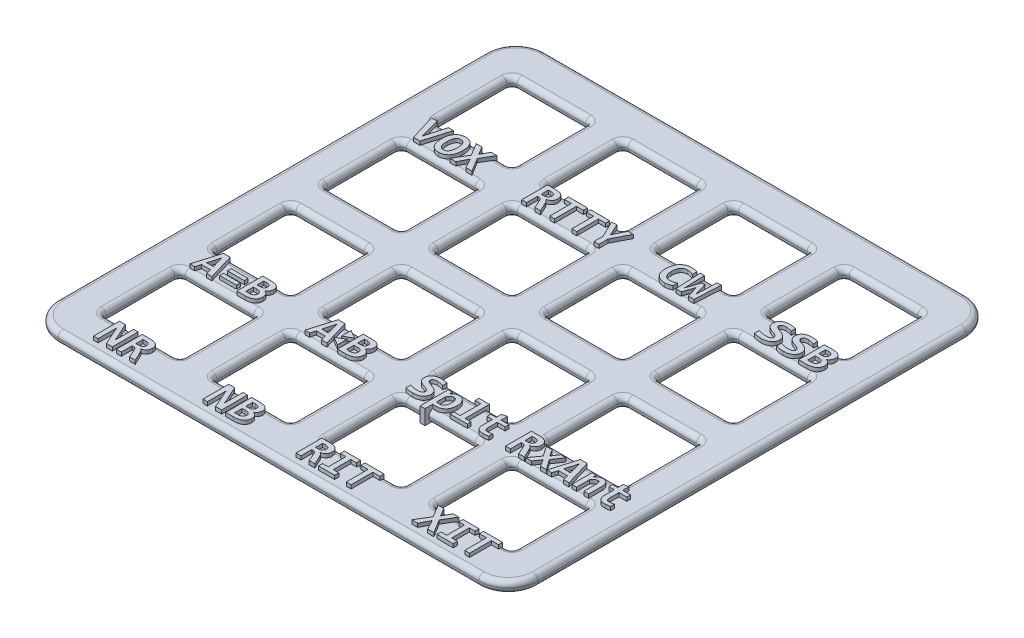
SolidWorks part; units mm, degrees
ref_plane "Front" through (0, 0, 0) normal (0, 0, 1) x (1, 0, 0)
ref_plane "Top" through (0, 0, 0) normal (0, 1, 0) x (1, 0, 0)
ref_plane "Right" through (0, 0, 0) normal (1, 0, 0) x (0, 0, -1)
sketch "Sketch1" plane through (0, 0, 0) normal (0, 1, 0) x (1, 0, 0)
  line L1 (-14.8807, -14.5355) -> (42.1193, -14.5355)
  line L2 (-18.8807, -18.5355) -> (-18.8807, -76.5355)
  line L3 (-14.8807, -80.5355) -> (42.1193, -80.5355)
  line L4 (46.1193, -18.5355) -> (46.1193, -76.5355)
  arc A0 (-14.8807, -14.5355) -> (-18.8807, -18.5355) centre (-14.8807, -18.5355) ccw
  arc A1 (46.1193, -18.5355) -> (42.1193, -14.5355) centre (42.1193, -18.5355) ccw
  arc A2 (42.1193, -80.5355) -> (46.1193, -76.5355) centre (42.1193, -76.5355) ccw
  arc A3 (-18.8807, -76.5355) -> (-14.8807, -80.5355) centre (-14.8807, -76.5355) ccw
  dimension "D1" = 65
  dimension "D2" = 66
extrude "main" add sketch "Sketch1" along normal blind 1.5
sketch "Sketch2" plane through (0, 1.5, 0) normal (0, 1, 0) x (1, 0, 0)
  line L0 (42.1193, -14.5355) -> (-14.8807, -14.5355) construction
  line L1 (-14.2307, -19.6855) -> (-3.5307, -19.6855)
  line L2 (-14.2307, -19.6855) -> (-14.2307, -30.3855)
  line L3 (-14.2307, -30.3855) -> (-3.5307, -30.3855)
  line L4 (-3.5307, -19.6855) -> (-3.5307, -30.3855)
  line L5 (-18.8807, -18.5355) -> (-18.8807, -76.5355) construction
  point P4 (-8.8807, -19.6855)
  dimension "D1" = 5.15
  dimension "D2" = 4.65
  dimension "D3" = 10.7
  dimension "D4" = 10.7
extrude "button hole 1" cut sketch "Sketch2" against normal through all
fillet "button fillet" radius 0.7 12 edges at (-8.8807, 0, 30.3855) (-8.8807, 1.5, 30.3855) (-8.8807, 0, 19.6855) (-8.8807, 1.5, 19.6855) (-3.5307, 0.75, 30.3855) (-3.5307, 0, 25.0355) (-3.5307, 0.75, 19.6855) (-3.5307, 1.5, 25.0355) (-14.2307, 0.75, 19.6855) (-14.2307, 0, 25.0355) (-14.2307, 0.75, 30.3855) (-14.2307, 1.5, 25.0355)
pattern_linear "buttons by 16" count 4 spacing 15 along (1, 0, 0) count 4 spacing 15 along (0, 0, 1) of "button fillet", "button hole 1"
fillet "outer edge fillet" radius 0.7 16 edges at (13.6193, 1.5, 14.5355) (13.6193, 0, 14.5355) (46.1193, 1.5, 47.5355) (46.1193, 0, 47.5355) (13.6193, 1.5, 80.5355) (13.6193, 0, 80.5355) (-18.8807, 1.5, 47.5355) (-18.8807, 0, 47.5355) (44.9477, 1.5, 15.7071) (44.9477, 1.5, 79.364) (-17.7092, 1.5, 79.364) (-17.7092, 1.5, 15.7071) (44.9477, 0, 15.7071) (44.9477, 0, 79.364) (-17.7092, 0, 79.364) (-17.7092, 0, 15.7071)
sketch "Lettering" plane through (0, 0, 0) normal (0, 1, 0) x (1, 0, 0)
  line L0 (45.4193, -49.1355) -> (-18.1807, -49.1355) construction
  line L1 (45.4783, -79.1355) -> (-16.5217, -79.1355) construction
  line L2 (45.4193, -76.5355) -> (45.4193, -18.5355) construction
  line L3 (-18.1807, -18.5355) -> (-18.1807, -76.5355) construction
  line L5 (45.4193, -64.1355) -> (-18.1807, -64.1355) construction
  line L6 (45.4193, -76.5355) -> (45.4193, -18.5355) construction
  line L7 (-18.1807, -18.5355) -> (-18.1807, -76.5355) construction
  line L8 (45.4193, -34.1355) -> (-18.1807, -34.1355) construction
  line L11 (-14.8807, -80.5355) -> (42.1193, -80.5355) construction
  line L16 (6.45, -61.6855) -> (5.3241, -61.0355)
  line L17 (5.3241, -61.0355) -> (5.3241, -62.3355)
  line L18 (5.3241, -62.3355) -> (6.45, -61.6855)
  line L19 (4.9405, -62.9814) -> (6.0628, -63.6376)
  line L20 (6.0628, -63.6376) -> (6.07, -62.3376)
  line L21 (6.07, -62.3376) -> (4.9405, -62.9814)
  line L26 (1.4693, -63.9855) -> (10.7693, -63.9855) construction
  circle A1 centre (5.6994, -61.6855) radius 0.3753 construction
  circle A2 centre (5.6911, -62.9855) radius 0.3753 construction
  text T0 "SSB" font "Consolas" height 3.5
  text T1 "CW" font "Consolas" height 3.5
  text T2 "RTTY" font "Consolas" height 3.5
  text T3 "VOX" font "Consolas" height 3.5
  text T4 "RxAnt" font "Consolas" height 3.5
  text T5 "Splt" font "Consolas" height 3.5
  text T6 "XIT" font "Consolas" height 3.5
  text T7 "A" font "Consolas" height 3.5
  text T9 "RIT" font "Consolas" height 3.5
  text T10 "NB" font "Consolas" height 3.5
  text T11 "NR" font "Consolas" height 3.5
  text T15 "A=B" font "Consolas" height 3.5
  text T17 "B" font "Consolas" height 3.5
  dimension "D1" = 46.4
  dimension "D2" = 16.4
  dimension "D3" = 1.4
  dimension "D4" = 31.4
  dimension "D5" = 1.3
  dimension "D6" = 1.3
  dimension "D7" = 1
extrude "lettering boss" add sketch "Lettering" along normal offset from surface (2 mm away) 0.5 up to face at (13.6193, 1.5, 47.5355) offset beyond the face yes
